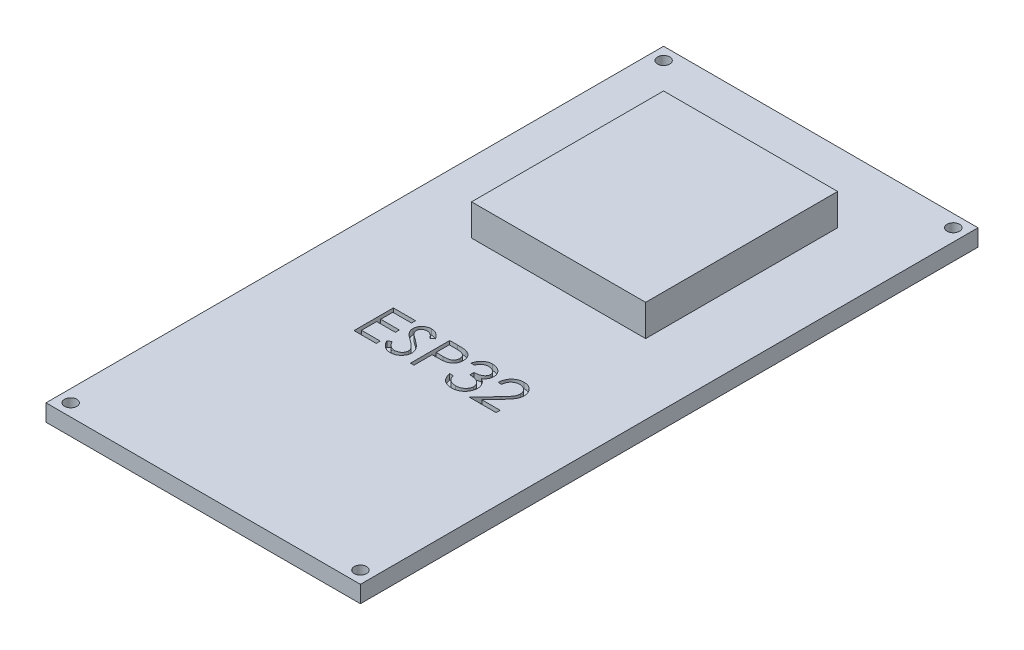
SolidWorks part; units mm, degrees
ref_plane "Front Plane" through (0, 0, 0) normal (0, 0, 1) x (1, 0, 0)
ref_plane "Top Plane" through (0, 0, 0) normal (0, 1, 0) x (1, 0, 0)
ref_plane "Right Plane" through (0, 0, 0) normal (1, 0, 0) x (0, 0, -1)
sketch "Sketch2" plane through (0, 0, 0) normal (0, 1, 0) x (1, 0, 0)
  line L1 (0, 0) -> (28, 0)
  line L2 (0, 0) -> (0, 55)
  line L3 (0, 55) -> (28, 55)
  line L4 (28, 0) -> (28, 55)
extrude "Boss-Extrude1" add sketch "Sketch2" along normal blind 1.5
sketch "Sketch3" plane through (0, 1.5, 0) normal (0, 1, 0) x (1, 0, 0)
  line L0 (0, 55) -> (0, 0) construction
  line L1 (6.25, 48.75) -> (21.75, 48.75)
  line L2 (6.25, 48.75) -> (6.25, 31.65)
  line L3 (6.25, 31.65) -> (21.75, 31.65)
  line L4 (21.75, 48.75) -> (21.75, 31.65)
  line L5 (28, 55) -> (0, 55) construction
  dimension "D1" = 6.25
  dimension "D2" = 15.5
  dimension "D3" = 17.1
  dimension "D4" = 6.25
extrude "Boss-Extrude2" add sketch "Sketch3" along normal blind 2.8
sketch "Sketch4" plane through (0, 1.5, 0) normal (0, 1, 0) x (1, 0, 0)
  text T0 "ESP32\r\n"
extrude "Cut-Extrude1" cut sketch "Sketch4" against normal blind 0.5
sketch "Sketch5" plane through (0, 1.5, 0) normal (0, 1, 0) x (1, 0, 0)
  line L0 (28, 55) -> (0, 55) construction
  line L1 (0, 55) -> (0, 0) construction
  circle A0 centre (1.1, 53.9) radius 0.55
  dimension "D1" = 1.1
  dimension "D3" = 1.1
  dimension "D2" = 1.1
extrude "Cut-Extrude2" cut sketch "Sketch5" against normal through all
ref_plane "Plane1" through (14, 0, 0) normal (1, 0, 0) x (0, 0, -1)
ref_plane "Plane2" through (0, 0, -27.5) normal (0, 0, -1) x (-1, 0, 0)
mirror "Mirror2" about plane through (14, 0, 0) normal (1, 0, 0) of "Cut-Extrude2" second plane through (0, 0, -27.5) second plane normal (0, 0, -1)
